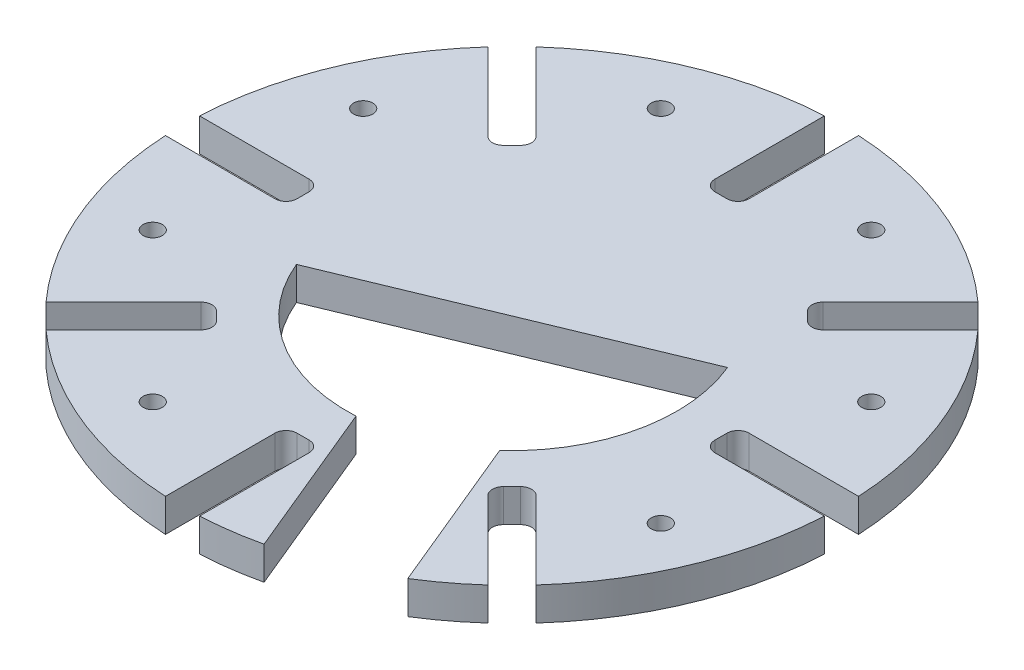
SolidWorks part; units mm, degrees
ref_plane "前视基准面" through (0, 0, 0) normal (0, 0, 1) x (1, 0, 0)
ref_plane "上视基准面" through (0, 0, 0) normal (0, 1, 0) x (1, 0, 0)
ref_plane "右视基准面" through (0, 0, 0) normal (1, 0, 0) x (0, 0, -1)
sketch "草图2" plane through (0, 0, 0) normal (0, 1, 0) x (1, 0, 0)
  line L0 (0, 0) -> (88.2448, 0) construction
  circle A0 centre (0, 0) radius 60
  dimension "D1" = 120
extrude "凸台-拉伸1" add sketch "草图2" along normal blind 6 contours A0
sketch "草图3" plane through (0, 6, 0) normal (0, 1, 0) x (1, 0, 0)
  line L0 (0, 0) -> (105.9564, 0) construction
  line L2 (38, 3.1) -> (98, 3.1)
  line L3 (38, 3.1) -> (38, -3.1)
  line L4 (38, -3.1) -> (98, -3.1)
  line L5 (98, 3.1) -> (98, -3.1)
  line L33 (24.678, -29.0621) -> (67.1044, -71.4885)
  line L34 (29.0621, -24.678) -> (24.678, -29.0621)
  line L35 (29.0621, -24.678) -> (71.4885, -67.1044)
  line L36 (71.4885, -67.1044) -> (67.1044, -71.4885)
  line L37 (-3.1, -38) -> (-3.1, -98)
  line L38 (3.1, -38) -> (-3.1, -38)
  line L39 (3.1, -38) -> (3.1, -98)
  line L40 (3.1, -98) -> (-3.1, -98)
  line L41 (-29.0621, -24.678) -> (-71.4885, -67.1044)
  line L42 (-24.678, -29.0621) -> (-29.0621, -24.678)
  line L43 (-24.678, -29.0621) -> (-67.1044, -71.4885)
  line L44 (-67.1044, -71.4885) -> (-71.4885, -67.1044)
  line L45 (-38, 3.1) -> (-98, 3.1)
  line L46 (-38, -3.1) -> (-38, 3.1)
  line L47 (-38, -3.1) -> (-98, -3.1)
  line L48 (-98, -3.1) -> (-98, 3.1)
  line L49 (-24.678, 29.0621) -> (-67.1044, 71.4885)
  line L50 (-29.0621, 24.678) -> (-24.678, 29.0621)
  line L51 (-29.0621, 24.678) -> (-71.4885, 67.1044)
  line L52 (-71.4885, 67.1044) -> (-67.1044, 71.4885)
  line L53 (3.1, 38) -> (3.1, 98)
  line L54 (-3.1, 38) -> (3.1, 38)
  line L55 (-3.1, 38) -> (-3.1, 98)
  line L56 (-3.1, 98) -> (3.1, 98)
  line L57 (29.0621, 24.678) -> (71.4885, 67.1044)
  line L58 (24.678, 29.0621) -> (29.0621, 24.678)
  line L59 (24.678, 29.0621) -> (67.1044, 71.4885)
  line L60 (67.1044, 71.4885) -> (71.4885, 67.1044)
  point P37 (0, 6)
  point P39 (0, 0)
  dimension "D1" = 6.2
  dimension "D2" = 38
  dimension "D3" = 60
extrude "切除-拉伸1" cut sketch "草图3" against normal blind 6
fillet "圆角1" radius 2 16 edges at (38, 3, 3.1) (38, 3, -3.1) (24.678, 3, 29.0621) (29.0621, 3, 24.678) (-3.1, 3, 38) (3.1, 3, 38) (-29.0621, 3, 24.678) (-24.678, 3, 29.0621) (-38, 3, 3.1) (-38, 3, -3.1) (-29.0621, 3, -24.678) (-24.678, 3, -29.0621) (-3.1, 3, -38) (3.1, 3, -38) (24.678, 3, -29.0621) (29.0621, 3, -24.678)
sketch "草图6" plane through (0, 6, 0) normal (0, 1, 0) x (1, 0, 0)
  line L0 (0, 0) -> (28.0301, -67.6706) construction
  line L1 (26.0922, -30.4763) -> (40.1777, -44.5618) construction
  line L2 (3.1, -59.9199) -> (3.1, -40) construction
  line L4 (-5.412, -13.0656) -> (13.0656, -5.412)
  line L5 (-5.412, -13.0656) -> (17.549, -68.4984)
  line L6 (17.549, -68.4984) -> (36.0266, -60.8447)
  line L7 (13.0656, -5.412) -> (36.0266, -60.8447)
  dimension "D1" = 20
  dimension "D2" = 70
  dimension "D3" = 60
extrude "切除-拉伸2" cut sketch "草图6" against normal blind 10 contours L7 L6 L5 L4
sketch "草图7" plane through (0, 6, 0) normal (0, 1, 0) x (1, 0, 0)
  line L0 (-76.5791, -31.7201) -> (69.7577, 28.8946) construction
  line L1 (-5.412, -13.0656) -> (13.0656, -5.412) construction
  line L2 (-27.7164, -11.4805) -> (27.7164, 11.4805)
  arc A0 (-27.7164, -11.4805) -> (27.7164, 11.4805) centre (0, 0) ccw
  dimension "D1" = 60
extrude "切除-拉伸3" cut sketch "草图7" against normal blind 10 contours A0 L2
sketch "草图8" plane through (0, 6, 0) normal (0, 1, 0) x (1, 0, 0)
  line L0 (0, 0) -> (46.194, 19.1342) construction
  line L1 (59.9199, 3.1) -> (40, 3.1) construction
  line L2 (30.4763, 26.0922) -> (44.5618, 40.1777) construction
  circle A0 centre (46.194, 19.1342) radius 1.75
  circle A1 centre (46.194, -19.1342) radius 1.75
  circle A3 centre (-19.1342, -46.194) radius 1.75
  circle A4 centre (-46.194, -19.1342) radius 1.75
  circle A5 centre (-46.194, 19.1342) radius 1.75
  circle A6 centre (-19.1342, 46.194) radius 1.75
  circle A7 centre (19.1342, 46.194) radius 1.75
  circle A8 centre (19.1342, -46.194) radius 1.75 [skipped]
  point P24 (0, 0)
  dimension "D1" = 3.5
  dimension "D2" = 50
  dimension "D3" = 8
extrude "切除-拉伸4" cut sketch "草图8" against normal blind 10
